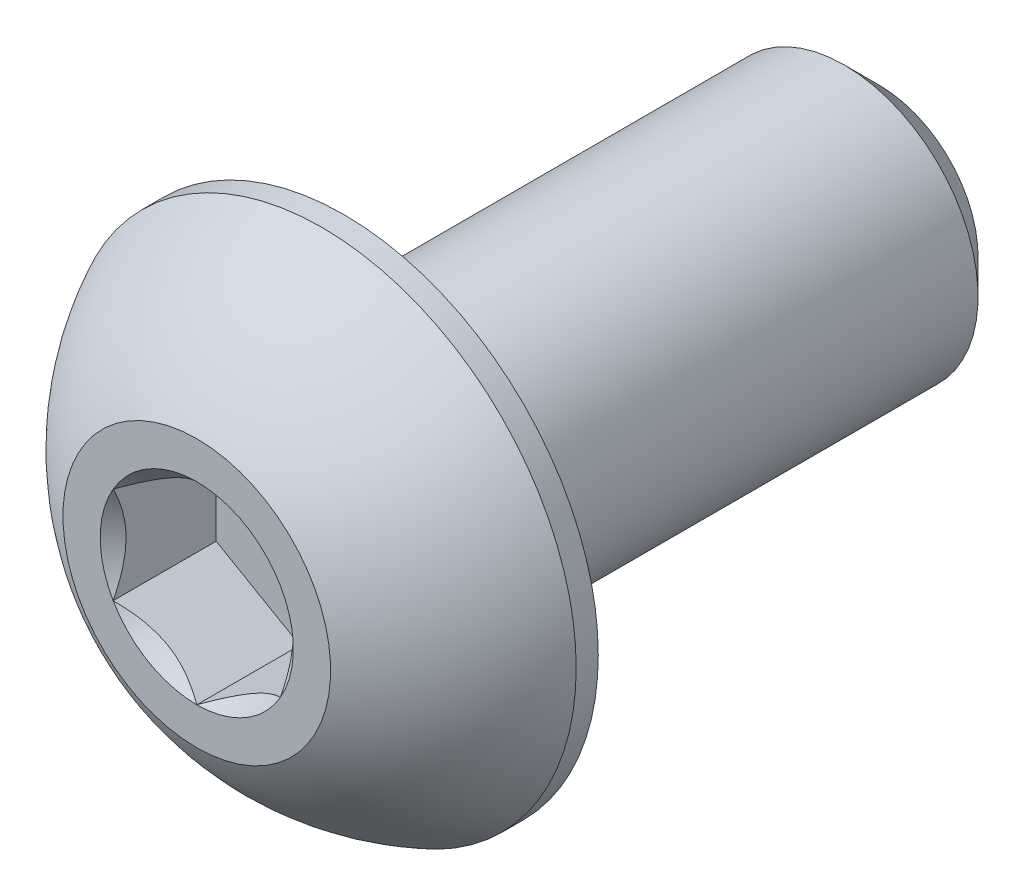
SolidWorks part; units mm, degrees
ref_plane "Front" through (0, 0, 0) normal (0, 0, 1) x (1, 0, 0)
ref_plane "Top" through (0, 0, 0) normal (0, 1, 0) x (1, 0, 0)
ref_plane "Right" through (0, 0, 0) normal (1, 0, 0) x (0, 0, -1)
sketch "Sketch1" plane through (0, 0, 0) normal (1, 0, 0) x (0, 0, -1)
  line L2 (2.2, 2) -> (10.2, 2)
  line L3 (10.2, 2) -> (10.2, 0)
  line L4 (10.2, 0) -> (2.2, 0)
  line L6 (1.87, 3.8) -> (2.2, 3.8) construction
  line L7 (10.2, 2) -> (10.2, -2) construction
  line L8 (0, 0) -> (2.2, 0) construction
  line L9 (2.2, 3.8) -> (2.2, -3.8) construction
  line L11 (2.2, 2) -> (2.2, 0)
  line L13 (0, 1.25) -> (0, -1.25) construction
  line L14 (0, 1.25) -> (0, 2) construction
  arc A3 (0, 2) -> (1.87, 3.8) centre (3.7264, 0) cw construction
  dimension "D1" = 0.33
revolve "Revolve1" add sketch "Sketch1" angle 360 mid plane about L4
sketch "Sketch3" plane through (0, 0, -10.2) normal (0, 0, -1) x (-1, 0, 0)
  circle A0 centre (0, 0) radius 2
curve "Helix/Spiral1" pitch 0.7 height 8.7 turns 12.4286
chamfer "Chamfer1" distance 0.525 angle 45 1 edges at (0, 2, -10.2)
sketch "Sketch7" plane through (0, 0, 0) normal (1, 0, 0) x (0, 0, -1)
  line L6 (1.87, 3.8) -> (2.2, 3.8) construction
  line L8 (0, 0) -> (2.2, 0) construction
  line L11 (2.2, 3.8) -> (2.2, -3.8) construction
  line L12 (1.87, 3.8) -> (2.2, 3.8)
  line L13 (0, 0) -> (2.2, 0)
  line L14 (0, 1.25) -> (0, -1.25) construction
  line L15 (2.2, 3.8) -> (2.2, 0)
  line L16 (0, 2) -> (0, 0)
  arc A2 (1.87, 3.8) -> (0, 2) centre (3.7264, 0) ccw construction
  arc A3 (1.87, 3.8) -> (0, 2) centre (3.7264, 0) ccw
revolve "Revolve2" add sketch "Sketch7" angle 360 mid plane about L13
sketch "Sketch5" plane through (0, 0, 0) normal (0, 0, 1) x (1, 0, 0)
  line L1 (1.25, -0.7217) -> (1.25, 0.7217)
  line L2 (1.25, 0.7217) -> (0, 1.4434)
  line L3 (0, 1.4434) -> (-1.25, 0.7217)
  line L4 (-1.25, 0.7217) -> (-1.25, -0.7217)
  line L5 (-1.25, -0.7217) -> (0, -1.4434)
  line L6 (0, -1.4434) -> (1.25, -0.7217)
  circle A0 centre (0, 0) radius 1.25 construction
extrude "Cut-Extrude2" cut sketch "Sketch5" against normal blind 1.54
sketch "Sketch6" plane through (0, 0, 0) normal (0, 0, 1) x (1, 0, 0)
  circle A0 centre (0, 0) radius 1.4434
extrude "Cut-Extrude3" cut sketch "Sketch6" against normal blind 1.54 draft 45
sketch "Sketch2" plane through (0, 0, 0) normal (1, 0, 0) x (0, 0, -1)
  line L0 (9.675, 2) -> (10.2875, 2)
  line L1 (10.2875, 2) -> (10.025, 1.5453)
  line L2 (10.025, 1.5453) -> (9.9375, 1.5453)
  line L3 (9.9375, 1.5453) -> (9.675, 2)
  line L4 (9.8062, 1.7727) -> (10.1562, 1.7727) construction
  dimension "D1" = 60
  dimension "D2" = 0.0875
  dimension "D3" = 0.35
sweep "Cut-Sweep1" [suppressed] cut profiles "Sketch2" path "Helix/Spiral1"
sketch "Sketch10" plane through (0, 0, 0) normal (1, 0, 0) x (0, 0, -1)
  line L0 (10.2, 2) -> (10.2, -2) construction
  point P0 (9.15, -2)
  dimension "D1" = 1.05
ref_axis "Center Axis 1" through (0, 0, -8.1113) along (0, 0, 1)
ref_plane "Contact Plane 1" through (0, 0, -2.2) normal (0, 0, -1) x (-1, 0, 0)
ref_plane "Contact Plane 2" through (0, 0, 0) normal (0, 0, 1) x (1, 0, 0)
equation "\"D3@Helix/Spiral1\" = \"Lg@Sketch1\" + \"D4@Helix/Spiral1\""
equation "\"D2@Sketch2\" = \"D4@Helix/Spiral1\" * .125"
equation "\"D3@Sketch2\" = \"D4@Helix/Spiral1\" * .5"
equation "\"D1@Chamfer1\" = \"D4@Helix/Spiral1\" * .75"
equation "\"D1@Cut-Extrude2\" = \"Head Ht@Sketch1\" * .7"
equation "\"D1@Sketch1\" = \"Head Ht@Sketch1\" * .15"
equation "\"D1@Sketch10\" = \"D4@Helix/Spiral1\" * 1.5"
equation "\"D1@Cut-Extrude3\" = \"D1@Cut-Extrude2\""
